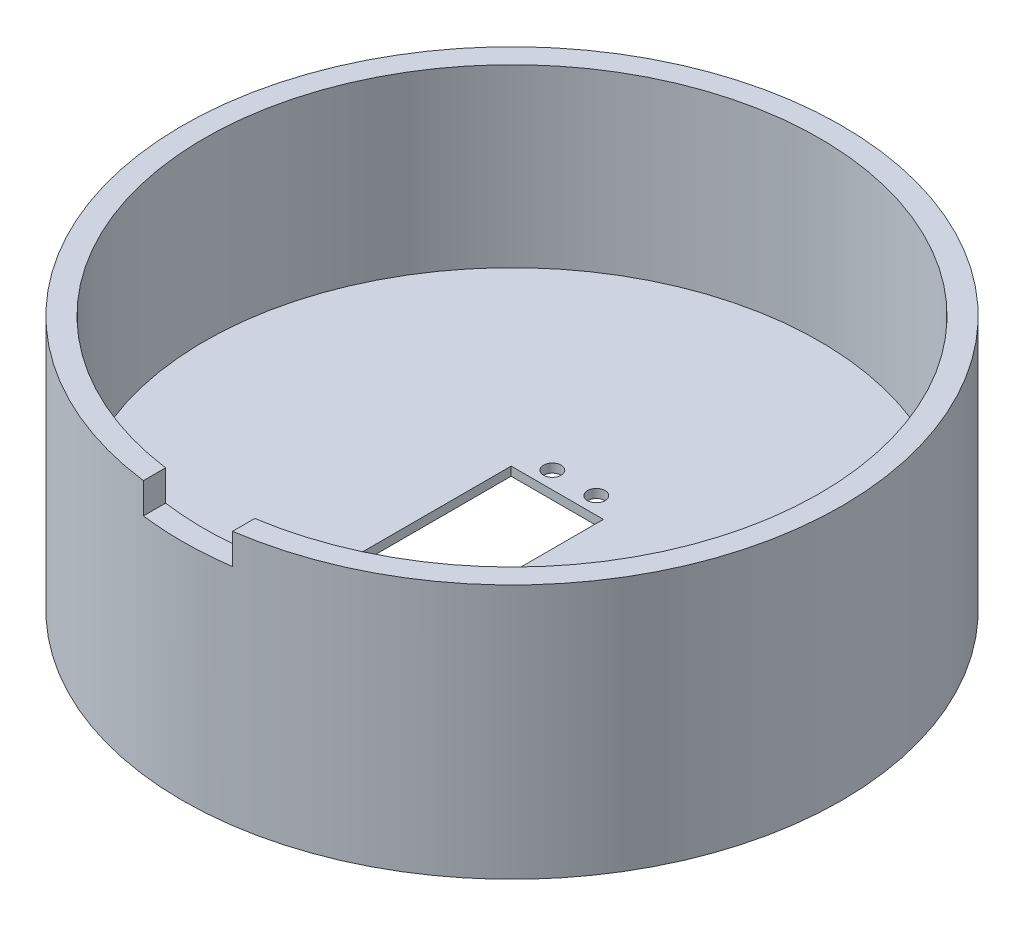
SolidWorks part; units mm, degrees
ref_plane "Plan de face" through (0, 0, 0) normal (0, 0, 1) x (1, 0, 0)
ref_plane "Plan de dessus" through (0, 0, 0) normal (0, 1, 0) x (1, 0, 0)
ref_plane "Plan de droite" through (0, 0, 0) normal (1, 0, 0) x (0, 0, -1)
sketch "Esquisse1" plane through (0, 0, 0) normal (0, 1, 0) x (1, 0, 0)
  line L0 (0, 17.15) -> (0, -30.7) construction
  line L1 (-10.5, 17.15) -> (10.5, 17.15) construction
  line L3 (-10.5, -30.7) -> (10.5, -30.7)
  line L5 (-10.5, 0) -> (10.5, 0) construction
  line L6 (-10.5, 10.3) -> (10.5, 10.3)
  line L7 (-5, -34.4507) -> (-5, 14.1793) construction
  line L8 (-10.5, -30.7) -> (10.5, -30.7)
  line L9 (-10.5, -30.7) -> (-10.5, -37.55) construction
  line L10 (-10.5, -37.55) -> (10.5, -37.55) construction
  line L11 (10.5, -30.7) -> (10.5, -37.55) construction
  line L12 (-10.5, 14.1793) -> (10.5, 14.1793) construction
  line L13 (-5, -34.4507) -> (-10.5, -34.4507) construction
  line L14 (-5, -34.4507) -> (10.5, -34.4507) construction
  line L15 (-10.5, 14.1793) -> (10.5, -34.4507) construction
  line L16 (-10.5, -34.4507) -> (10.5, 14.1793) construction
  line L17 (0, -10.1357) -> (-10.5, -10.1357) construction
  line L18 (0, -30.7) -> (0, -37.55) construction
  line L19 (-10.5, 10.3) -> (-10.5, -30.7)
  line L20 (-10.5, 17.15) -> (-10.5, 10.3) construction
  line L21 (10.5, 10.3) -> (10.5, -30.7)
  line L22 (10.5, 17.15) -> (10.5, 10.3) construction
  circle A0 centre (0, 0) radius 75
  circle A1 centre (-5, 14.1793) radius 2
  circle A2 centre (-5, -34.4507) radius 2
  circle A3 centre (5, -34.4507) radius 2
  circle A4 centre (5, 14.1793) radius 2
  circle A5 centre (0, 0) radius 70
  dimension "D1" = 150
  dimension "D6" = 4
  dimension "D7" = 4
  dimension "D2" = 17.15
  dimension "D3" = 6.85
  dimension "D4" = 41
  dimension "D5" = 6.85
  dimension "D8" = 48.63
  dimension "D9" = 21
  dimension "D10" = 5
  dimension "D11" = 5
extrude "Boss.-Extru.1" add sketch "Esquisse1" against normal blind 2 contours A0 A5 | A5 A4 L6 L21 L3 L19 A1 A2 A3 region at (-72.8787, 0, 0) region at (-68.0201, 0, 0)
extrude "Boss.-Extru.2" add sketch "Esquisse1<4>" along normal blind 40 contours A0 A5 region at (-72.8787, 0, 0)
sketch "Esquisse1<4>" plane through (0, 0, 0) normal (0, 1, 0) x (1, 0, 0) same geometry as "Esquisse1"
ref_plane "Plan1" through (0, 0, 75) normal (0, 0, 1) x (1, 0, 0)
sketch "Esquisse2" plane through (0, 0, 75) normal (0, 0, 1) x (1, 0, 0)
  line L1 (-9.4741, 40.3764) -> (10.6593, 40.3764)
  line L2 (-9.4741, 40.3764) -> (-9.4741, 33.0395)
  line L3 (-9.4741, 33.0395) -> (10.6593, 33.0395)
  line L4 (10.6593, 40.3764) -> (10.6593, 33.0395)
extrude "Enlèv. mat.-Extru.1" cut sketch "Esquisse2" against normal blind 40
extrude "Boss.-Extru.3" add sketch "Esquisse1<5>" against normal blind 18 contours A0 A5 region at (-72.8787, 0, 0)
sketch "Esquisse1<5>" plane through (0, 0, 0) normal (0, 1, 0) x (1, 0, 0) same geometry as "Esquisse1"
